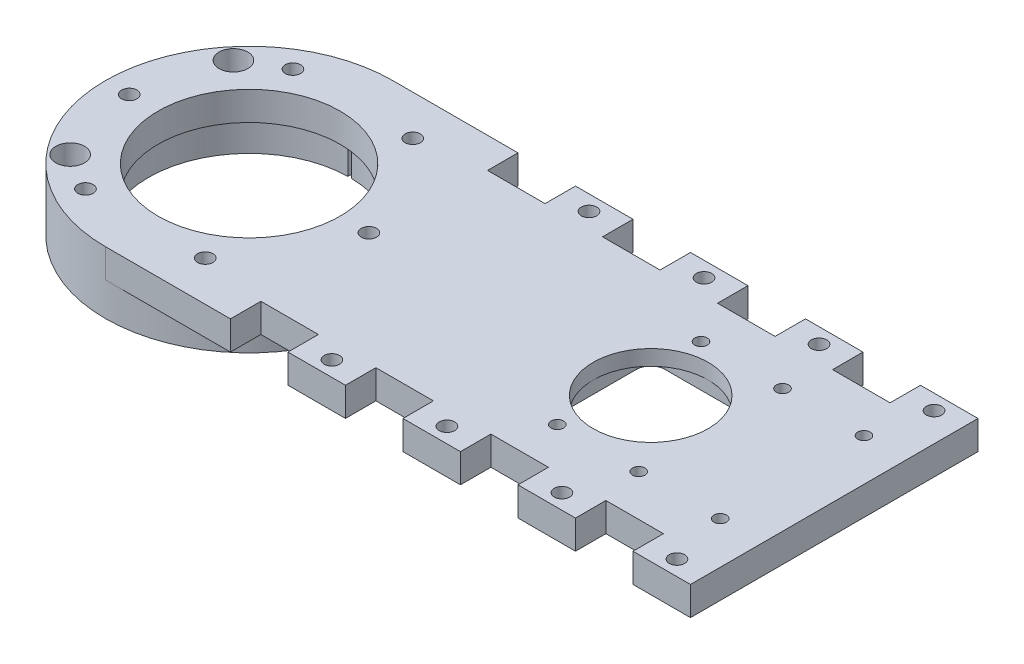
SolidWorks part; units mm, degrees
ref_plane "Front Plane" through (0, 0, 0) normal (0, 0, 1) x (1, 0, 0)
ref_plane "Top Plane" through (0, 0, 0) normal (0, 1, 0) x (1, 0, 0)
ref_plane "Right Plane" through (0, 0, 0) normal (1, 0, 0) x (0, 0, -1)
sketch "Sketch1" plane through (0, 0, 0) normal (0, 1, 0) x (1, 0, 0)
  line L0 (11, 0) -> (-83.81, 0) construction
  line L1 (-17.3, 17.8) -> (38.3, 17.8)
  line L2 (-17.3, 17.8) -> (-17.3, -17.8)
  line L3 (-17.3, -17.8) -> (38.3, -17.8)
  line L4 (38.3, 17.8) -> (38.3, -17.8)
  line L5 (-12.2, 12.2) -> (33.2, 12.2)
  line L6 (-12.2, 12.2) -> (-12.2, -12.2)
  line L7 (-12.2, -12.2) -> (33.2, -12.2)
  line L8 (33.2, 12.2) -> (33.2, -12.2)
  circle A0 centre (0, 0) radius 11 construction
  circle A1 centre (-83.81, 0) radius 21 construction
  circle A2 centre (-83.81, 0) radius 15 construction
  circle A3 centre (-4.5, 15) radius 1.3
  circle A4 centre (-4.5, 15) radius 2.25 construction
  circle A5 centre (12.5, 15) radius 1.3
  circle A6 centre (29.5, 15) radius 1.3
  circle A7 centre (29.5, -15) radius 1.3
  circle A8 centre (12.5, -15) radius 1.3
  circle A9 centre (-4.5, -15) radius 1.3
  circle A10 centre (0, 0) radius 12
  point P16 (33.2, 0)
  dimension "D1" = 22
  dimension "D2" = 42
  dimension "D3" = 30
  dimension "D9" = 2.6
  dimension "D10" = 4.5
  dimension "D7" = 2.8
  dimension "D18" = 24
  dimension "D4" = 83.81
  dimension "D5" = 5.1
  dimension "D6" = 5.1
  dimension "D8" = 17
  dimension "D11" = 2.8
  dimension "D12" = 4.5
  dimension "D14" = 3.7
  dimension "D15" = 7.7
  dimension "D16" = 15
  dimension "D17" = 2.8
  dimension "D13" = 3
extrude "Boss-Extrude1" add sketch "Sketch1" against normal blind 2.8 contours L4 L1 L2 L3 A8 L5 L8 L7 L6 A3 A5 A6 A7 A9 region at (10.5, 0, -17.1398)
extrude "Boss-Extrude2" add sketch "Sketch1<5>" along normal blind 3.2 contours L4 L1 L2 L3 A8 L5 L8 L7 L6 A3 A5 A6 A7 A9 | L8 L5 L6 L7 A10 region at (10.5, 0, -17.1398) region at (17.7479, 0, 0)
sketch "Sketch1<5>" plane through (0, 0, 0) normal (0, 1, 0) x (1, 0, 0) same geometry as "Sketch1"
fillet "Fillet1" radius 3 4 edges at (33.2, -1.4, -12.2) (-12.2, -1.4, -12.2) (-12.2, -1.4, 12.2) (33.2, -1.4, 12.2)
sketch "Sketch2" plane through (0, 0, 0) normal (0, 1, 0) x (1, 0, 0)
  line L0 (-17.3, 17.8) -> (-59.6613, 17.8)
  line L1 (-17.3, -17.8) -> (-59.6613, -17.8)
  line L2 (-17.3, 17.8) -> (-17.3, -17.8)
  arc A0 (-59.6613, 17.8) -> (-59.6613, -17.8) centre (-83.81, 0) ccw
  circle A1 centre (-83.81, 0) radius 19
  dimension "D1" = 60
  dimension "D2" = 38
extrude "Boss-Extrude3" add sketch "Sketch2" along normal up to surface and the other way up to surface up to face at (12.5, 3.2, 16.3) other way up to face at (12.5, -2.8, 16.3)
sketch "Sketch3" plane through (0, -2.8, 0) normal (0, 1, 0) x (1, 0, 0)
  line L0 (-83.81, 30) -> (-83.81, 0) construction
  line L1 (-83.81, 0) -> (-62.81, 0) construction
  line L2 (-84.185, 20.9967) -> (-84.185, 25.9967)
  line L3 (-84.185, 25.9967) -> (-83.435, 25.9967)
  line L4 (-83.435, 25.9967) -> (-83.435, 20.9967)
  line L5 (-84.185, -25.9967) -> (-83.435, -25.9967)
  line L6 (-84.185, -20.9967) -> (-84.185, -25.9967)
  line L7 (-83.435, -25.9967) -> (-83.435, -20.9967)
  circle A0 centre (-83.81, 0) radius 30
  arc A1 (-59.6613, 17.8) -> (-59.6613, -17.8) centre (-83.81, 0) ccw construction
  arc A2 (-84.185, 20.9967) -> (-84.185, -20.9967) centre (-83.81, 0) ccw
  arc A3 (-83.435, -20.9967) -> (-83.435, 20.9967) centre (-83.81, 0) ccw
  dimension "D1" = 42
  dimension "D2" = 5
  dimension "D3" = 0.75
extrude "Boss-Extrude4" add sketch "Sketch3" against normal blind 7
sketch "Sketch4" plane through (0, 3.2, 0) normal (0, 1, 0) x (1, 0, 0)
  circle A0 centre (-58.81, 0) radius 1.6
  circle A1 centre (-71.31, -21.6506) radius 1.6
  circle A2 centre (-96.31, -21.6506) radius 1.6
  circle A3 centre (-108.81, 0) radius 1.6
  circle A4 centre (-96.31, 21.6506) radius 1.6
  circle A5 centre (-71.31, 21.6506) radius 1.6
  point P2 (0, 0)
  point P4 (0, 0)
  point P16 (-83.81, 0)
  point P17 (-69.9108, 23.3158)
  dimension "D1" = 3.2
  dimension "D2" = 25
  dimension "D3" = 6
extrude "Cut-Extrude1" cut sketch "Sketch4" against normal through all
sketch "Sketch5" plane through (0, -9.8, 0) normal (0, -1, 0) x (-1, 0, 0)
  circle A0 centre (96.31, 21.6506) radius 2.8
  circle A1 centre (108.81, 0) radius 2.8
  circle A2 centre (96.31, -21.6506) radius 2.8
  circle A3 centre (71.31, -21.6506) radius 2.8
  circle A4 centre (58.81, 0) radius 2.8
  circle A5 centre (71.31, 21.6506) radius 2.8
  point P4 (-81.3111, 1.9748)
  point P15 (83.81, 0)
  dimension "D1" = 5.6
  dimension "D2" = 6
extrude "Cut-Extrude2" cut sketch "Sketch5" against normal blind 3.5
sketch "Sketch6" plane through (0, 3.2, 0) normal (0, 1, 0) x (1, 0, 0)
  line L0 (38.3, 17.8) -> (38.3, 30)
  line L1 (38.3, 30) -> (-83.81, 30)
  line L2 (-59.6613, 17.8) -> (38.3, 17.8) construction
  line L3 (-59.6613, 17.8) -> (38.3, 17.8)
  circle A0 centre (-83.81, 0) radius 30 construction
  arc A1 (-59.6613, 17.8) -> (-83.81, 30) centre (-83.81, 0) ccw
  point P3 (38.3, 30)
  point P8 (0, 0)
  point P9 (-83.81, 30)
  point P10 (-75.7396, 28.8941)
  point P11 (-83.81, 30)
extrude "Boss-Extrude5" add sketch "Sketch6" against normal up to surface (6 mm away) up to face at (12.5, -2.8, 16.3)
mirror "Mirror1" about plane through (0, 0, 0) normal (0, 0, 1) of "Boss-Extrude5"
sketch "Sketch7" plane through (0, -2.8, 0) normal (0, -1, 0) x (1, 0, 0)
  line L0 (-83.81, -30) -> (38.3, -30) construction
  line L1 (26.3, -30) -> (14.3, -30)
  line L2 (26.3, -30) -> (26.3, -23.65)
  line L3 (26.3, -23.65) -> (14.3, -23.65)
  line L4 (14.3, -30) -> (14.3, -23.65)
  line L5 (38.3, -30) -> (38.3, 30) construction
  line L6 (2.3, -23.65) -> (-9.7, -23.65)
  line L7 (2.3, -30) -> (2.3, -23.65)
  line L8 (-9.7, -30) -> (-9.7, -23.65)
  line L9 (2.3, -30) -> (-9.7, -30)
  line L10 (-21.7, -23.65) -> (-33.7, -23.65)
  line L11 (-21.7, -30) -> (-21.7, -23.65)
  line L12 (-33.7, -30) -> (-33.7, -23.65)
  line L13 (-21.7, -30) -> (-33.7, -30)
  line L14 (-45.7, -23.65) -> (-57.7, -23.65)
  line L15 (-45.7, -30) -> (-45.7, -23.65)
  line L16 (-57.7, -30) -> (-57.7, -23.65)
  line L17 (-45.7, -30) -> (-57.7, -30)
  dimension "D1" = 12
  dimension "D2" = 12
  dimension "D3" = 6.35
  dimension "D5" = 12
  dimension "D4" = 4
extrude "Cut-Extrude3" cut sketch "Sketch7" against normal through all
mirror "Mirror2" about plane through (0, 0, 0) normal (0, 0, 1) of "Cut-Extrude3"
sketch "Sketch8" plane through (0, -2.8, 0) normal (0, -1, 0) x (1, 0, 0)
  line L0 (-45.7, -30) -> (-33.7, -30) construction
  line L3 (-45.7, -30) -> (-57.7, -30) construction
  circle A0 centre (-39.7, -26.825) radius 1.6
  circle A1 centre (-15.7, -26.825) radius 1.6
  circle A2 centre (8.3, -26.825) radius 1.6
  circle A3 centre (32.3, -26.825) radius 1.6
  point P4 (-39.7, -30)
  dimension "D1" = 3.2
  dimension "D2" = 3.175
  dimension "D4" = 24
  dimension "D3" = 4
extrude "Cut-Extrude4" cut sketch "Sketch8" against normal through all
mirror "Mirror3" about plane through (0, 0, 0) normal (0, 0, 1) of "Cut-Extrude4"
sketch "Sketch9" plane through (0, 3.2, 0) normal (0, 1, 0) x (1, 0, 0)
  line L8 (-83.81, 0) -> (-104.1102, -17.0339) construction
  line L9 (-101.8835, -19.6875) -> (-100.6987, -16.4323)
  line L10 (-100.6987, -16.4323) -> (-102.9254, -13.7787)
  line L11 (-102.9254, -13.7787) -> (-106.3369, -14.3802)
  line L12 (-106.3369, -14.3802) -> (-107.5217, -17.6354)
  line L13 (-107.5217, -17.6354) -> (-105.295, -20.2891)
  line L14 (-105.295, -20.2891) -> (-101.8835, -19.6875)
  line L15 (-83.81, 0) -> (-108.81, 0) construction
  circle A3 centre (-104.1102, -17.0339) radius 1.6
  circle A4 centre (-104.1102, -17.0339) radius 3 construction
  circle A6 centre (-104.1102, 17.0339) radius 1.6
  circle A7 centre (-104.1102, 17.0339) radius 3 construction
  point P10 (-101.3734, -12.9476)
  point P12 (-106.1485, -14.5242)
  point P13 (0, 0)
  point P14 (-107.2929, -17.6028)
  point P15 (0, 0)
  point P18 (-105.9971, -20.1924)
  point P19 (-101.812, -15.1055)
  dimension "D1" = 3.2
  dimension "D2" = 6
  dimension "D3" = 40
  dimension "D4" = 26.5
extrude "Cut-Extrude5" cut sketch "Sketch9" against normal through all contours A3 | A6 region at (-104.1102, 3.2, 17.0339) region at (-104.1102, 3.2, -17.0339)
sketch "Sketch10" plane through (0, 3.2, 0) normal (0, 1, 0) x (1, 0, 0)
  line L35 (14.3, -23.65) -> (26.3, -23.65)
  line L36 (26.3, -23.65) -> (26.3, -30)
  line L37 (26.3, -30) -> (38.3, -30)
  line L38 (38.3, -30) -> (38.3, 30)
  line L39 (38.3, 30) -> (26.3, 30)
  line L40 (26.3, 30) -> (26.3, 23.65)
  line L41 (26.3, 23.65) -> (14.3, 23.65)
  line L42 (14.3, 23.65) -> (14.3, 30)
  line L43 (14.3, 30) -> (2.3, 30)
  line L44 (2.3, 30) -> (2.3, 23.65)
  line L45 (2.3, 23.65) -> (-9.7, 23.65)
  line L46 (-9.7, 23.65) -> (-9.7, 30)
  line L47 (-9.7, 30) -> (-21.7, 30)
  line L48 (-21.7, 30) -> (-21.7, 23.65)
  line L49 (-21.7, 23.65) -> (-33.7, 23.65)
  line L50 (-33.7, 23.65) -> (-33.7, 30)
  line L51 (-33.7, 30) -> (-45.7, 30)
  line L52 (-45.7, 30) -> (-45.7, 23.65)
  line L53 (-45.7, 23.65) -> (-57.7, 23.65)
  line L54 (-57.7, 23.65) -> (-57.7, 30)
  line L55 (-57.7, 30) -> (-83.81, 30)
  line L56 (-83.81, -30) -> (-57.7, -30)
  line L57 (-57.7, -30) -> (-57.7, -23.65)
  line L58 (-57.7, -23.65) -> (-45.7, -23.65)
  line L59 (-45.7, -23.65) -> (-45.7, -30)
  line L60 (-45.7, -30) -> (-33.7, -30)
  line L61 (-33.7, -30) -> (-33.7, -23.65)
  line L62 (-33.7, -23.65) -> (-21.7, -23.65)
  line L63 (-21.7, -23.65) -> (-21.7, -30)
  line L64 (-21.7, -30) -> (-9.7, -30)
  line L65 (-9.7, -30) -> (-9.7, -23.65)
  line L66 (-9.7, -23.65) -> (2.3, -23.65)
  line L67 (2.3, -23.65) -> (2.3, -30)
  line L68 (2.3, -30) -> (14.3, -30)
  line L69 (14.3, -30) -> (14.3, -23.65)
  line L70 (14.3, -23.65) -> (26.3, -23.65)
  line L71 (26.3, -23.65) -> (26.3, -30)
  line L72 (26.3, -30) -> (38.3, -30)
  line L73 (38.3, -30) -> (38.3, 30)
  line L74 (38.3, 30) -> (26.3, 30)
  line L75 (26.3, 30) -> (26.3, 23.65)
  line L76 (26.3, 23.65) -> (14.3, 23.65)
  line L77 (14.3, 23.65) -> (14.3, 30)
  line L78 (14.3, 30) -> (2.3, 30)
  line L79 (2.3, 30) -> (2.3, 23.65)
  line L80 (2.3, 23.65) -> (-9.7, 23.65)
  line L81 (-9.7, 23.65) -> (-9.7, 30)
  line L82 (-9.7, 30) -> (-21.7, 30)
  line L83 (-21.7, 30) -> (-21.7, 23.65)
  line L84 (-21.7, 23.65) -> (-33.7, 23.65)
  line L85 (-33.7, 23.65) -> (-33.7, 30)
  line L86 (-33.7, 30) -> (-45.7, 30)
  line L87 (-45.7, 30) -> (-45.7, 23.65)
  line L88 (-45.7, 23.65) -> (-57.7, 23.65)
  line L89 (-57.7, 23.65) -> (-57.7, 30)
  line L90 (-57.7, 30) -> (-83.81, 30)
  line L91 (-83.81, -30) -> (-57.7, -30)
  line L92 (-57.7, -30) -> (-57.7, -23.65)
  line L93 (-57.7, -23.65) -> (-45.7, -23.65)
  line L94 (-45.7, -23.65) -> (-45.7, -30)
  line L95 (-45.7, -30) -> (-33.7, -30)
  line L96 (-33.7, -30) -> (-33.7, -23.65)
  line L97 (-33.7, -23.65) -> (-21.7, -23.65)
  line L98 (-21.7, -23.65) -> (-21.7, -30)
  line L99 (-21.7, -30) -> (-9.7, -30)
  line L100 (-9.7, -30) -> (-9.7, -23.65)
  line L101 (-9.7, -23.65) -> (2.3, -23.65)
  line L102 (2.3, -23.65) -> (2.3, -30)
  line L103 (2.3, -30) -> (14.3, -30)
  line L104 (14.3, -30) -> (14.3, -23.65)
  circle A0 centre (-104.1102, 17.0339) radius 3 construction
  arc A1 (-83.81, 30) -> (-83.81, -30) centre (-83.81, 0) ccw
  arc A2 (-83.81, 30) -> (-83.81, -30) centre (-83.81, 0) ccw
  circle A3 centre (-104.1102, 17.0339) radius 3
  circle A4 centre (-104.1102, -17.0339) radius 3 construction
  circle A5 centre (-104.1102, -17.0339) radius 3
  dimension "D1" = 0
extrude "Cut-Extrude7" cut sketch "Sketch10" against normal blind 7 contours A3 | A5 region at (-104.1102, 3.2, -17.0339) region at (-104.1102, 3.2, 17.0339)
